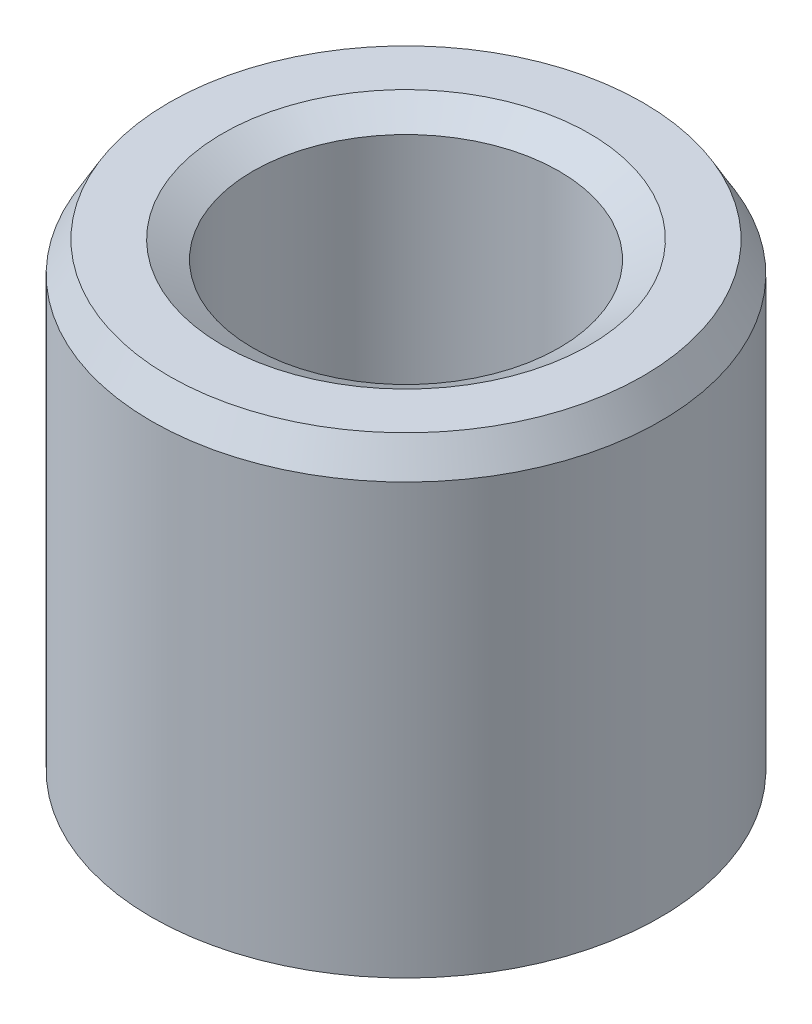
SolidWorks part; units mm, degrees
ref_plane "Front Plane" through (0, 0, 0) normal (0, 0, 1) x (1, 0, 0)
ref_plane "Top Plane" through (0, 0, 0) normal (0, 1, 0) x (1, 0, 0)
ref_plane "Right Plane" through (0, 0, 0) normal (1, 0, 0) x (0, 0, -1)
sketch "Sketch1" plane through (0, 0, 0) normal (0, 1, 0) x (1, 0, 0)
  circle A0 centre (0, 0) radius 10
  dimension "SLEEVE_OD" = 20
extrude "Boss-Extrude1" add sketch "Sketch1" along normal blind 18.7587
sketch "Sketch2" plane through (0, 0, 0) normal (0, 1, 0) x (1, 0, 0)
  circle A0 centre (0, 0) radius 6.0176
  dimension "BORE_D" = 12.0351
extrude "Cut-Extrude1" cut sketch "Sketch2" along normal through all
chamfer "Chamfer1" distance 1.1912 angle 30 4 edges at (0, 18.7587, 6.0176) (0, 0, 6.0176) (0, 0, 10) (0, 18.7587, 10) first distance on face at (0, 18.7587, 6.0176) first distance on face at (0, 0, 6.0176) first distance on face at (0, 18.7587, 10)
